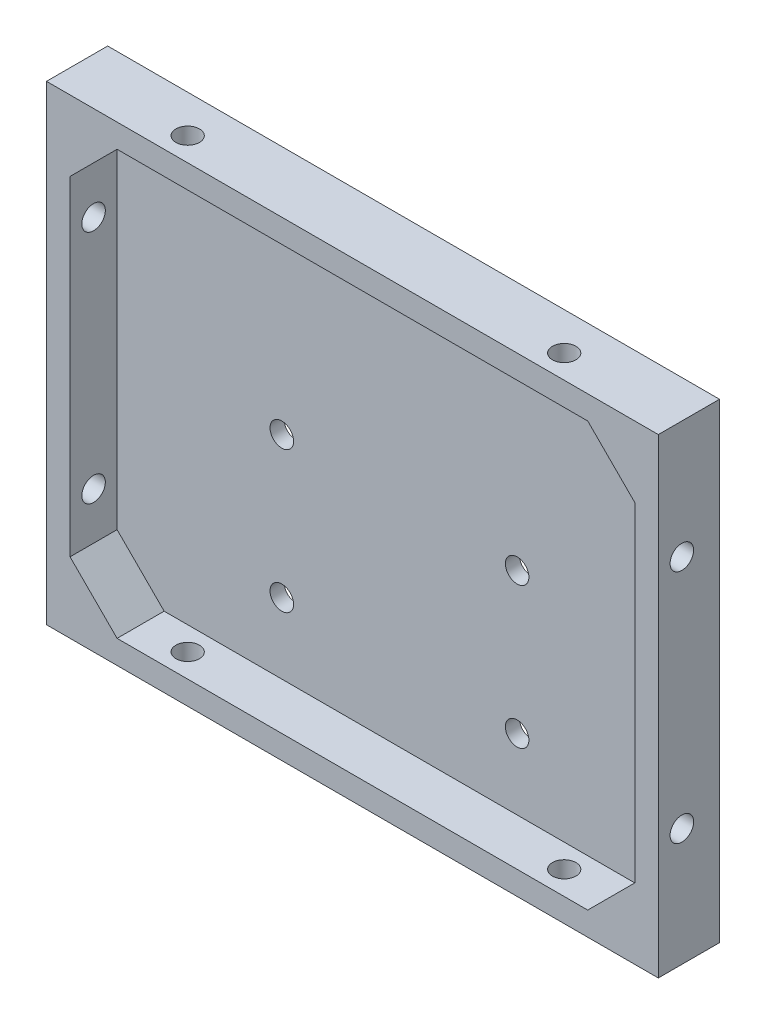
SolidWorks part; units mm, degrees
ref_plane "Plan de face" through (0, 0, 0) normal (0, 0, 1) x (1, 0, 0)
ref_plane "Plan de dessus" through (0, 0, 0) normal (0, 1, 0) x (1, 0, 0)
ref_plane "Plan de droite" through (0, 0, 0) normal (1, 0, 0) x (0, 0, -1)
sketch "Esquisse1" plane through (0, 0, 0) normal (0, 0, 1) x (1, 0, 0)
  line L0 (44.1184, 33.7284) -> (54.1184, 33.7284)
  line L1 (-75.8816, 33.7284) -> (44.1184, 33.7284)
  line L2 (-75.8816, 33.7284) -> (-75.8816, -66.2716)
  line L3 (-75.8816, -66.2716) -> (54.1184, -66.2716)
  line L4 (54.1184, 23.7284) -> (54.1184, -66.2716)
  line L5 (54.1184, 33.7284) -> (54.1184, 23.7284)
  point P6 (54.1184, 33.7284)
  dimension "D1" = 130
  dimension "D2" = 100
extrude "Boss.-Extru.1" add sketch "Esquisse1" along normal blind 13
shell "Coque1" thickness 5 removed face at (-10.8816, -16.2716, 13)
sketch "Esquisse2" plane through (-75.8816, 0, 0) normal (-1, 0, 0) x (0, 0, 1)
  line L0 (13, 33.7284) -> (13, -66.2716) construction
  line L1 (13, 33.7284) -> (0, 33.7284) construction
  line L2 (13, -66.2716) -> (0, -66.2716) construction
  circle A0 centre (8, 8.7284) radius 2.5
  circle A1 centre (8, -41.2716) radius 2.5
  dimension "D1" = 5
  dimension "D2" = 5
  dimension "D3" = 5
  dimension "D4" = 5
  dimension "D5" = 25
  dimension "D6" = 25
extrude "Enlèv. mat.-Extru.1" cut sketch "Esquisse2" against normal up to surface (130 mm away) contours A1 | A0 region at (-75.8816, -41.2716, 8) up to face at (54.1184, -16.2716, 6.5)
sketch "Esquisse3" plane through (0, -66.2716, 0) normal (0, -1, 0) x (1, 0, 0)
  line L0 (-75.8816, 13) -> (54.1184, 13) construction
  line L2 (54.1184, 13) -> (54.1184, 0) construction
  line L3 (-75.8816, 13) -> (-75.8816, 0) construction
  circle A0 centre (-50.8816, 8) radius 2.5
  circle A1 centre (29.1184, 8) radius 2.5
  dimension "D1" = 5
  dimension "D2" = 5
  dimension "D3" = 5
  dimension "D4" = 5
  dimension "D5" = 25
  dimension "D6" = 25
extrude "Enlèv. mat.-Extru.2" cut sketch "Esquisse3" against normal up to surface (100 mm away) up to face at (-10.8816, 33.7284, 6.5)
sketch "Esquisse4" plane through (0, 0, 3) normal (0, 0, 1) x (1, 0, 0)
  line L0 (-60.8816, 28.7284) -> (-70.8816, 18.7284)
  line L1 (49.1184, 28.7284) -> (-70.8816, 28.7284) construction
  line L2 (-70.8816, 28.7284) -> (-70.8816, -61.2716) construction
  line L3 (-70.8816, 18.7284) -> (-70.8816, 28.7284)
  line L4 (-70.8816, 28.7284) -> (-60.8816, 28.7284)
  line L5 (49.1184, 28.7284) -> (49.1184, 18.7284)
  line L6 (49.1184, -61.2716) -> (49.1184, 28.7284) construction
  line L7 (49.1184, 18.7284) -> (39.1184, 28.7284)
  line L8 (39.1184, 28.7284) -> (49.1184, 28.7284)
  line L9 (49.1184, 28.7284) -> (-70.8816, 28.7284) construction
  line L10 (49.1184, -61.2716) -> (49.1184, -51.2716)
  line L11 (49.1184, -51.2716) -> (39.1184, -61.2716)
  line L12 (-70.8816, -61.2716) -> (49.1184, -61.2716) construction
  line L13 (39.1184, -61.2716) -> (49.1184, -61.2716)
  line L14 (-60.8816, -61.2716) -> (-70.8816, -51.2716)
  line L15 (-70.8816, 28.7284) -> (-70.8816, -61.2716) construction
  line L16 (-70.8816, -51.2716) -> (-70.8816, -61.2716)
  line L17 (-70.8816, -61.2716) -> (-60.8816, -61.2716)
  dimension "D1" = 10
  dimension "D2" = 10
  dimension "D3" = 10
  dimension "D4" = 10
  dimension "D5" = 10
  dimension "D6" = 10
  dimension "D7" = 10
  dimension "D8" = 10
extrude "Boss.-Extru.2" add sketch "Esquisse4" along normal up to surface (10 mm away) up to face at (-10.8816, -16.2716, 13)
sketch "Esquisse6" plane through (0, 0, 3) normal (0, 0, 1) x (1, 0, 0)
  line L0 (-75.8816, -66.2716) -> (54.1184, -66.2716) construction
  line L1 (54.1184, -66.2716) -> (54.1184, 33.7284) construction
  line L2 (-75.8816, 33.7284) -> (-75.8816, -66.2716) construction
  circle A0 centre (-35.8816, -46.2716) radius 2.5
  circle A1 centre (14.1184, -46.2716) radius 2.5
  circle A2 centre (14.1184, -16.2716) radius 2.5
  circle A3 centre (-35.8816, -16.2716) radius 2.5
  dimension "D1" = 5
  dimension "D2" = 5
  dimension "D3" = 5
  dimension "D4" = 5
  dimension "D5" = 20
  dimension "D6" = 20
  dimension "D7" = 50
  dimension "D8" = 50
  dimension "D9" = 30
  dimension "D10" = 40
  dimension "D11" = 40
  dimension "D12" = 40
extrude "Enlèv. mat.-Extru.3" cut sketch "Esquisse6" against normal up to surface (3 mm away) up to face at (-10.8816, -16.2716, 0)
